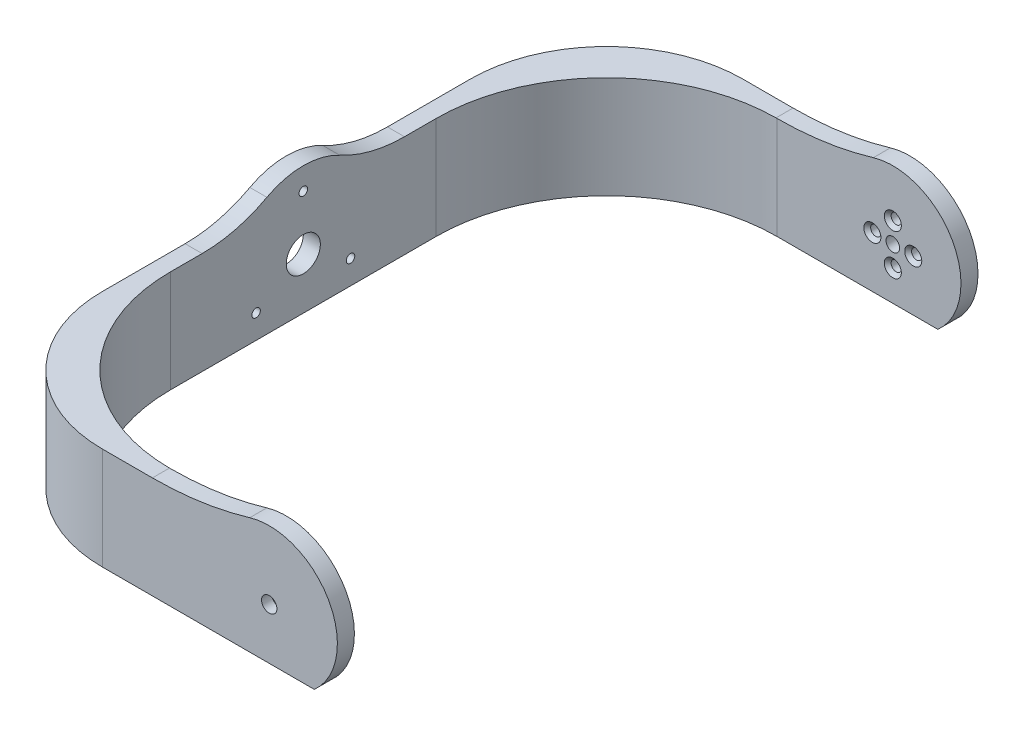
SolidWorks part; units mm, degrees
material "Polylactic Acid (PLA)"
ref_plane "Front Plane" through (0, 0, 0) normal (0, 0, 1) x (1, 0, 0)
ref_plane "Top Plane" through (0, 0, 0) normal (0, 1, 0) x (1, 0, 0)
ref_plane "Right Plane" through (0, 0, 0) normal (1, 0, 0) x (0, 0, -1)
sketch "Sketch1" plane through (0, 0, 0) normal (0, 0, 1) x (1, 0, 0)
  line L1 (0, 0) -> (89, 0)
  line L2 (0, 0) -> (0, 30)
  line L3 (0, 30) -> (89, 30)
  line L4 (89, 0) -> (89, 30)
  dimension "D1" = 89
  dimension "D2" = 30
extrude "Boss-Extrude1" add sketch "Sketch1" along normal mid plane 188
sketch "Sketch2" plane through (0, 0, 0) normal (0, 0, 1) x (1, 0, 0)
  line L0 (89, 0) -> (89, 30) construction
  line L2 (75.7712, 0) -> (102.2288, 0)
  line L4 (0, 0) -> (89, 0) construction
  arc A0 (102.2288, 0) -> (75.7712, 0) centre (89, 15) ccw
  dimension "D2" = 20
  dimension "D3" = 0
extrude "Boss-Extrude2" add sketch "Sketch2" along normal mid plane 188
sketch "Sketch4" plane through (0, 0, 0) normal (1, 0, 0) x (0, 0, -1)
  line L0 (94, 30) -> (94, 0) construction
  line L1 (-89, 55.7624) -> (89, 55.7624)
  line L2 (-89, 55.7624) -> (-89, -3.9412)
  line L3 (-89, -3.9412) -> (89, -3.9412)
  line L4 (89, 55.7624) -> (89, -3.9412)
  line L5 (-94, 30) -> (-94, 0) construction
  dimension "D1" = 5
  dimension "D2" = 5
extrude "Cut-Extrude2" cut sketch "Sketch4" along normal blind 150 from offset 5
ref_axis "Axis1" through (89, 15, -89) along (0, 0, -1)
sketch "Sketch5" plane through (0, 0, -94) normal (0, 0, -1) x (-1, 0, 0)
  line L1 (-89, 15) -> (-95, 15) construction
  line L2 (-89, 15) -> (-89, 21) construction
  circle A0 centre (-89, 15) radius 2
  circle A1 centre (-95, 15) radius 1.5
  circle A2 centre (-89, 21) radius 1.5
  circle A3 centre (-83, 15) radius 1.5
  circle A4 centre (-89, 9) radius 1.5
  dimension "D1" = 4
  dimension "D4" = 90
  dimension "D2" = 3
  dimension "D3" = 6
extrude "Cut-Extrude3" cut sketch "Sketch5" against normal blind 10
fillet "Fillet1" radius 100 2 edges at (75.7712, 30, 91.5) (75.7712, 30, -91.5)
fillet "Fillet2" radius 50 2 edges at (5, 15, -89) (5, 15, 89)
fillet "Fillet3" radius 40 2 edges at (0, 15, -94) (0, 15, 94)
sketch "Sketch7" plane through (0, 0, 0) normal (-1, 0, 0) x (0, 0, 1)
  line L1 (0, -16.5) -> (0, 16.5) construction
  line L3 (54, 0) -> (-54, 0) construction
  line L5 (-16.7705, 0) -> (16.7705, 0)
  arc A0 (16.7705, 0) -> (-16.7705, 0) centre (0, 15) ccw
  dimension "D1" = 45
  dimension "D2" = 15
extrude "Boss-Extrude3" add sketch "Sketch7" against normal up to surface (5 mm away) up to face at (5, 15, 0)
sketch "Sketch8" plane through (0, 0, 89) normal (0, 0, -1) x (-1, 0, 0)
  circle A0 centre (-89, 15) radius 2.25
  dimension "D1" = 4.5
extrude "Cut-Extrude5" cut sketch "Sketch8" against normal up to surface (5 mm away) up to face at (66.8245, 20.1489, 94)
fillet "Fillet4" radius 40 2 edges at (2.5, 30, -16.7705) (2.5, 30, 16.7705)
sketch "Sketch10" plane through (0, 0, 0) normal (-1, 0, 0) x (0, 0, 1)
  line L0 (0, 15) -> (-13.8564, 7) construction
  line L1 (0, 15) -> (-13.8564, 7) construction
  line L2 (0, -16.5) -> (0, 16.5) construction
  line L3 (-89, 15) -> (-94, 15) construction
  line L4 (0, 15) -> (0, 31) construction
  circle A0 centre (-13.8564, 7) radius 1.25
  circle A1 centre (0, 31) radius 1.25
  circle A2 centre (13.8564, 7) radius 1.25
  circle A3 centre (0, 15) radius 5
  dimension "D1" = 2.5
  dimension "D3" = 10
  dimension "D2" = 3
  dimension "D4" = 120
extrude "Cut-Extrude6" cut sketch "Sketch10" against normal up to surface (5 mm away) up to face at (5, 23.7421, 0)
chamfer "Chamfer1" distance 1 angle 45 4 edges at (89, 7.5, -89) (95, 13.5, -89) (89, 19.5, -89) (83, 13.5, -89)
sketch "Sketch11" plane through (0, 0, 89) normal (0, 0, -1) x (-1, 0, 0)
  circle A0 centre (-89, 15) radius 4
  dimension "D1" = 8
extrude "Cut-Extrude7" cut sketch "Sketch11" against normal blind 2
